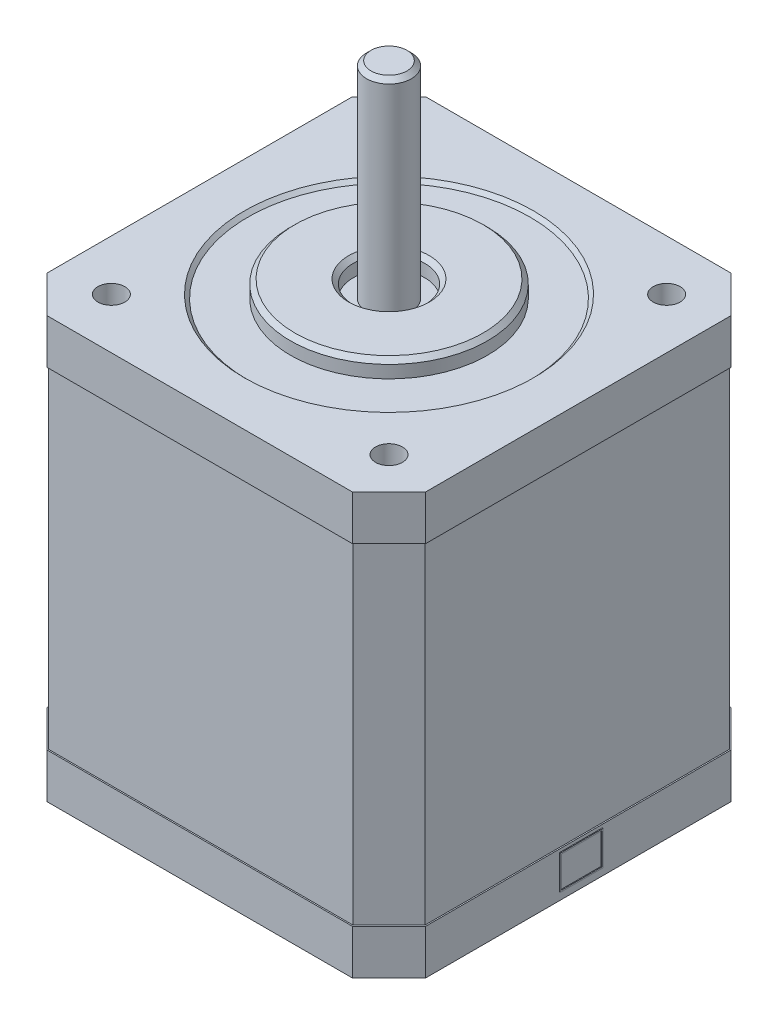
SolidWorks part; units mm, degrees
ref_plane "Front Plane" through (0, 0, 0) normal (0, 0, 1) x (1, 0, 0)
ref_plane "Top Plane" through (0, 0, 0) normal (0, 1, 0) x (1, 0, 0)
ref_plane "Right Plane" through (0, 0, 0) normal (1, 0, 0) x (0, 0, -1)
sketch "Sketch1" plane through (0, 0, 0) normal (0, 1, 0) x (1, 0, 0)
  line L1 (-21, 21) -> (21, 21)
  line L2 (-21, 21) -> (-21, -21)
  line L3 (-21, -21) -> (21, -21)
  line L4 (21, 21) -> (21, -21)
  line L5 (-21, 21) -> (21, -21) construction
  line L6 (-21, -21) -> (21, 21) construction
  point P0 (0, 0)
  dimension "D1" = 42
  dimension "D2" = 42
extrude "Boss-Extrude1" add sketch "Sketch1" along normal blind 47
chamfer "Chamfer1" distance 4 angle 45 4 edges at (-21, 23.5, -21) (21, 23.5, -21) (21, 23.5, 21) (-21, 23.5, 21)
sketch "Sketch6" plane through (0, 47, 0) normal (0, 1, 0) x (1, 0, 0)
  line L16 (17.0621, 21.15) -> (-17.0621, 21.15)
  line L17 (-17.0621, 21.15) -> (-21.15, 17.0621)
  line L18 (-21.15, 17.0621) -> (-21.15, -17.0621)
  line L19 (-21.15, -17.0621) -> (-17.0621, -21.15)
  line L20 (-17.0621, -21.15) -> (17.0621, -21.15)
  line L21 (17.0621, -21.15) -> (21.15, -17.0621)
  line L22 (21.15, -17.0621) -> (21.15, 17.0621)
  line L23 (21.15, 17.0621) -> (17.0621, 21.15)
  line L24 (17.0621, 21.15) -> (-17.0621, 21.15)
  line L25 (-17.0621, 21.15) -> (-21.15, 17.0621)
  line L26 (-21.15, 17.0621) -> (-21.15, -17.0621)
  line L27 (-21.15, -17.0621) -> (-17.0621, -21.15)
  line L28 (-17.0621, -21.15) -> (17.0621, -21.15)
  line L29 (17.0621, -21.15) -> (21.15, -17.0621)
  line L30 (21.15, -17.0621) -> (21.15, 17.0621)
  line L31 (21.15, 17.0621) -> (17.0621, 21.15)
  dimension "D1" = 0.15
extrude "Boss-Extrude4" add sketch "Sketch6" against normal blind 5
sketch "Sketch7" plane through (0, 0, 0) normal (0, -1, 0) x (1, 0, 0)
  line L16 (-21.15, 17.0621) -> (-21.15, -17.0621)
  line L17 (-21.15, -17.0621) -> (-17.0621, -21.15)
  line L18 (-17.0621, -21.15) -> (17.0621, -21.15)
  line L19 (17.0621, -21.15) -> (21.15, -17.0621)
  line L20 (21.15, -17.0621) -> (21.15, 17.0621)
  line L21 (21.15, 17.0621) -> (17.0621, 21.15)
  line L22 (17.0621, 21.15) -> (-17.0621, 21.15)
  line L23 (-17.0621, 21.15) -> (-21.15, 17.0621)
  line L24 (-21.15, 17.0621) -> (-21.15, -17.0621)
  line L25 (-21.15, -17.0621) -> (-17.0621, -21.15)
  line L26 (-17.0621, -21.15) -> (17.0621, -21.15)
  line L27 (17.0621, -21.15) -> (21.15, -17.0621)
  line L28 (21.15, -17.0621) -> (21.15, 17.0621)
  line L29 (21.15, 17.0621) -> (17.0621, 21.15)
  line L30 (17.0621, 21.15) -> (-17.0621, 21.15)
  line L31 (-17.0621, 21.15) -> (-21.15, 17.0621)
  dimension "D1" = 0.15
extrude "Boss-Extrude5" add sketch "Sketch7" against normal blind 5
sketch "Sketch2" plane through (0, 47, 0) normal (0, 1, 0) x (1, 0, 0)
  circle A0 centre (0, 0) radius 16.25
  dimension "D1" = 32.5
extrude "Cut-Extrude1" cut sketch "Sketch2" against normal blind 0.4
sketch "Sketch3" plane through (0, 46.6, 0) normal (0, 1, 0) x (1, 0, 0)
  circle A0 centre (0, 0) radius 4
  circle A1 centre (0, 0) radius 11
  dimension "D1" = 8
  dimension "D2" = 22
extrude "Boss-Extrude2" add sketch "Sketch3" along normal blind 1.9
sketch "Sketch4" plane through (0, 46.6, 0) normal (0, 1, 0) x (1, 0, 0)
  circle A0 centre (0, 0) radius 2.5
  dimension "D1" = 5
extrude "Boss-Extrude3" add sketch "Sketch4" along normal blind 23
chamfer "Chamfer2" distance 0.5 angle 45 4 edges at (0, 48.5, 4) (0, 48.5, 11) (0, 69.6, 2.5) (0, 46.6, 16.25)
sketch "Sketch5" plane through (0, 47, 0) normal (0, 1, 0) x (1, 0, 0)
  circle A0 centre (-15.5, 15.5) radius 1.5
  circle A1 centre (15.5, 15.5) radius 1.5
  circle A2 centre (15.5, -15.5) radius 1.5
  circle A3 centre (-15.5, -15.5) radius 1.5
  point P12 (0, 0)
  dimension "D1" = 15.5
  dimension "D2" = 15.5
  dimension "D3" = 3
  dimension "D4" = 4
extrude "Cut-Extrude2" cut sketch "Sketch5" against normal blind 5
sketch "Sketch8" plane through (21.15, 0, 0) normal (1, 0, 0) x (0, 0, -1)
  line L0 (17.0621, 0) -> (-17.0621, 0) construction
  line L1 (-1.9802, 4.5) -> (2.5198, 4.5)
  line L2 (-1.9802, 4.5) -> (-1.9802, 1)
  line L3 (-1.9802, 1) -> (2.5198, 1)
  line L4 (2.5198, 4.5) -> (2.5198, 1)
  line L5 (-1.9802, 4.5) -> (2.5198, 1) construction
  line L6 (-1.9802, 1) -> (2.5198, 4.5) construction
  line L7 (-2.1302, 4.65) -> (2.6698, 4.65)
  line L8 (2.6698, 4.65) -> (2.6698, 0.85)
  line L9 (-2.1302, 0.85) -> (2.6698, 0.85)
  line L10 (-2.1302, 4.65) -> (-2.1302, 0.85)
  point P0 (0.2698, 2.75)
  dimension "D1" = 1
  dimension "D2" = 3.5
  dimension "D3" = 4.5
  dimension "D4" = 0.15
extrude "Boss-Extrude6" add sketch "Sketch8" along normal blind 0.1
